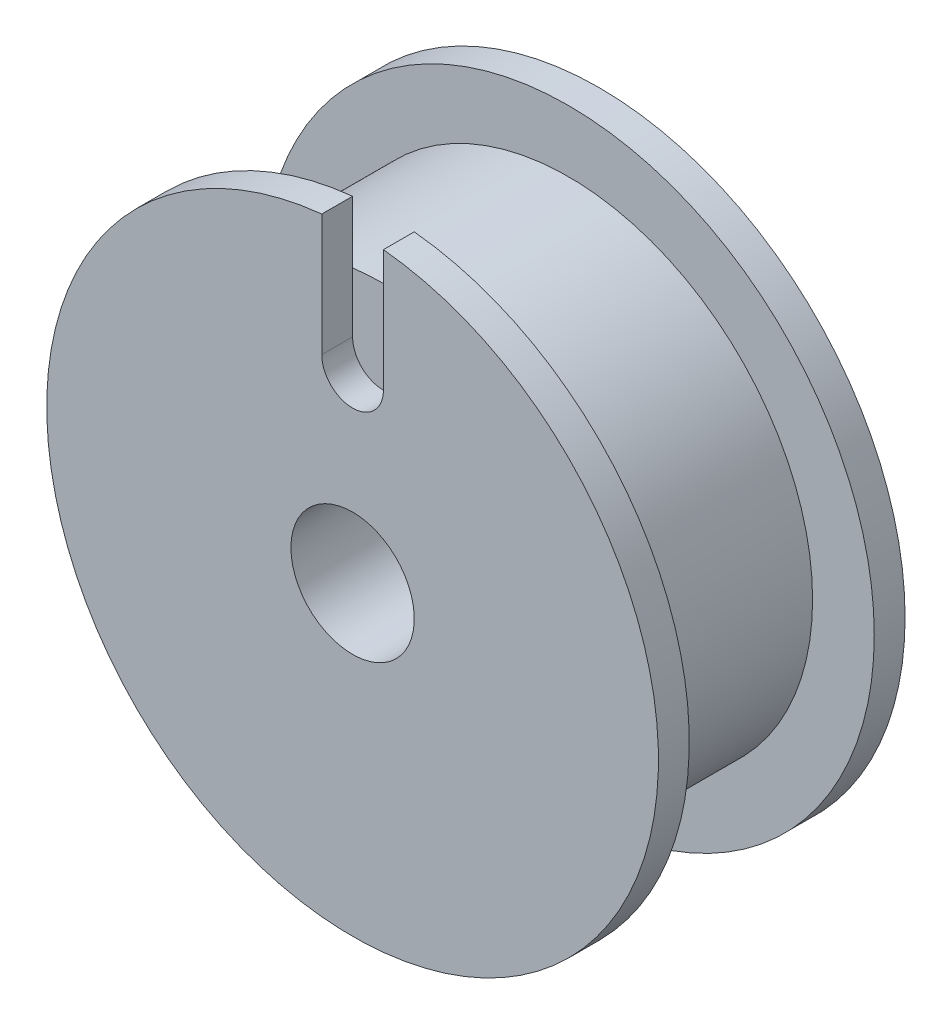
SolidWorks part; units mm, degrees
ref_plane "Front Plane" through (0, 0, 0) normal (0, 0, 1) x (1, 0, 0)
ref_plane "Top Plane" through (0, 0, 0) normal (0, 1, 0) x (1, 0, 0)
ref_plane "Right Plane" through (0, 0, 0) normal (1, 0, 0) x (0, 0, -1)
sketch "Sketch1" plane through (15.3043, 0, 0) normal (1, 0, 0) x (0, 0, -1)
  line L0 (93.4456, 24.7035) -> (-9.017, 24.7035) construction
  line L1 (65.6556, 40.4515) -> (65.6556, 8.9555) construction
  line L2 (67.2431, 40.4515) -> (65.6556, 40.4515) construction
  line L3 (67.2431, 40.4515) -> (67.2431, 8.9555) construction
  line L4 (67.2431, 37.2765) -> (76.7681, 37.2765) construction
  line L5 (76.7681, 40.4515) -> (76.7681, 8.9555) construction
  line L6 (76.7681, 40.4515) -> (78.3556, 40.4515) construction
  line L7 (78.3556, 40.4515) -> (78.3556, 8.9555) construction
  line L8 (22.225, 24.7035) -> (9.525, 24.7035)
  line L9 (65.6556, 40.4515) -> (65.6556, 27.8785)
  line L10 (67.2431, 40.4515) -> (65.6556, 40.4515)
  line L11 (67.2431, 40.4515) -> (67.2431, 37.2765)
  line L12 (67.2431, 37.2765) -> (76.7681, 37.2765)
  line L13 (76.7681, 40.4515) -> (76.7681, 37.2765)
  line L14 (76.7681, 40.4515) -> (78.3556, 40.4515)
  line L15 (78.3556, 40.4515) -> (78.3556, 27.8785)
  line L16 (93.4456, 27.8785) -> (-1.5875, 27.8785) construction
  line L17 (93.4456, 27.8785) -> (-1.5875, 27.8785)
revolve "Revolve1" add sketch "Sketch1" angle 360 about L8 region at (15.3043, 33.0671, -72.0056)
sketch "Sketch2" plane through (0, 0, -65.6556) normal (0, 0, -1) x (-1, 0, 0)
  line L0 (-15.3043, 40.4515) -> (-15.3043, 8.9555) construction
  line L1 (-15.3043, 40.4515) -> (-15.3043, 8.9555)
  line L2 (-15.3043, 40.4515) -> (-15.3043, 34.1015) construction
  line L3 (-13.7168, 40.4515) -> (-13.7168, 34.1015)
  line L4 (-16.8918, 40.4515) -> (-16.8918, 34.1015)
  arc A0 (-13.7168, 40.4515) -> (-16.8918, 40.4515) centre (-15.3043, 40.4515) ccw
  arc A1 (-16.8918, 34.1015) -> (-13.7168, 34.1015) centre (-15.3043, 34.1015) ccw
  point P2 (-15.3043, 37.2765)
  circle M11 centre (-15.3043, 24.7035) radius 15.748
  dimension "D1" = 1.5875
  dimension "D2" = 6.35
extrude "Cut-Extrude1" cut sketch "Sketch2" along normal up to surface (1.5875 mm away) contours A1 L1 L3 M11 | A1 L4 L1 M11 region at (14.5317, 36.6314, -65.6556) region at (16.0769, 36.6314, -65.6556) up to face at (2.7313, 24.7035, -67.2431)
